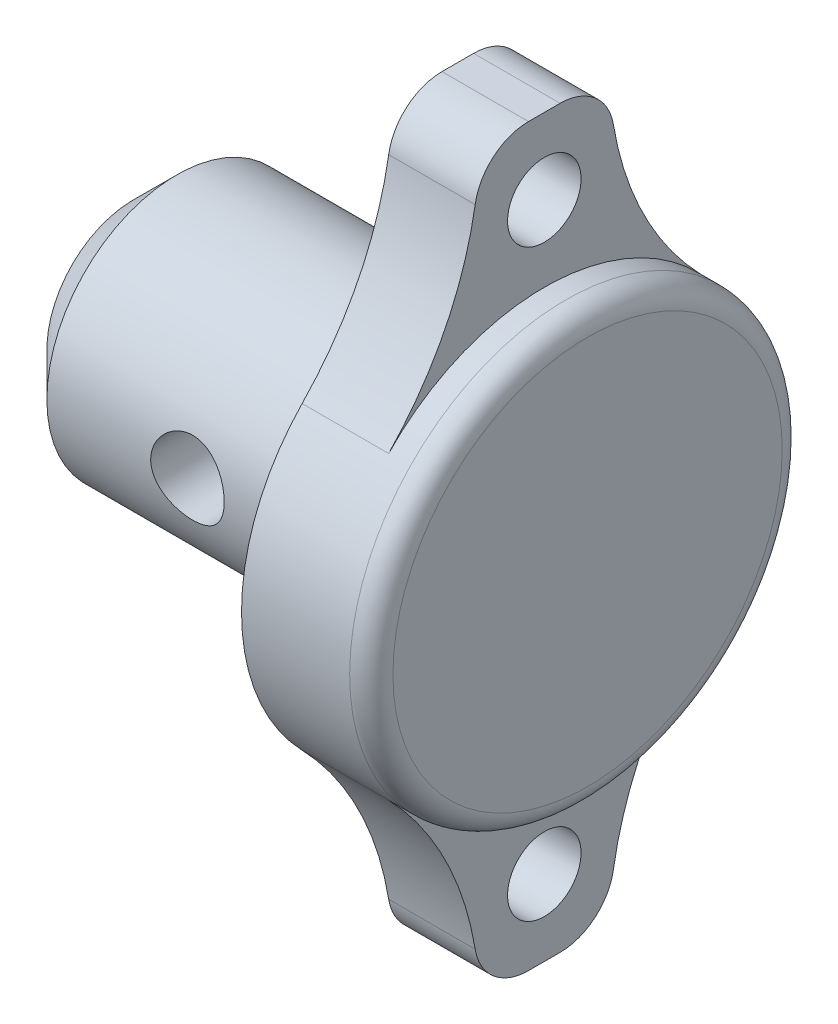
SolidWorks part; units mm, degrees
ref_plane "Alzado" through (0, 0, 0) normal (0, 0, 1) x (1, 0, 0)
ref_plane "Planta" through (0, 0, 0) normal (0, 1, 0) x (1, 0, 0)
ref_plane "Vista lateral" through (0, 0, 0) normal (1, 0, 0) x (0, 0, -1)
sketch "Croquis1" plane through (0, 0, 0) normal (1, 0, 0) x (0, 0, -1)
  circle A0 centre (0, 0) radius 6
  dimension "D1" = 12
extrude "Saliente-Extruir1" add sketch "Croquis1" along normal mid plane 15
sketch "Croquis2" plane through (7.5, 0, 0) normal (1, 0, 0) x (0, 0, -1)
  circle A0 centre (0, 0) radius 10
  dimension "D1" = 20
extrude "Saliente-Extruir2" add sketch "Croquis2" along normal blind 6
sketch "Croquis3" plane through (7.5, 0, 0) normal (-1, 0, 0) x (0, 0, 1)
  circle A0 centre (0, 0) radius 6
  circle A1 centre (0, 0) radius 8.5
  dimension "D1" = 17
extrude "Cortar-Extruir1" cut sketch "Croquis3" against normal blind 2.5
sketch "Croquis4" plane through (7.5, 0, 0) normal (-1, 0, 0) x (0, 0, 1)
  line L0 (0, 0) -> (0, -4.1911) construction
  line L1 (3, -9.5394) -> (3, -17)
  line L2 (3, -17) -> (-3, -17)
  line L3 (-3, -9.5394) -> (-3, -17)
  circle A2 centre (0, -13.5) radius 1.7
  circle A5 centre (0, 0) radius 10 construction
  arc A6 (-3, -9.5394) -> (3, -9.5394) centre (0, 0) ccw
  point P9 (0, -17)
  dimension "D3" = 3.4
  dimension "D1" = 6
  dimension "D2" = 17
  dimension "D4" = 13.5
extrude "Saliente-Extruir3" add sketch "Croquis4" against normal blind 4
fillet "Redondeo1" radius 15 2 edges at (9.5, -9.5394, -3) (9.5, -9.5394, 3)
sketch "Croquis5" plane through (0, 0, 0) normal (0, 0, 1) x (1, 0, 0)
  line L0 (7.5, 10) -> (7.5, -6.9415) construction
  circle A0 centre (1, 0) radius 1.7
  dimension "D1" = 3.4
  dimension "D2" = 6.5
extrude "Cortar-Extruir2" cut sketch "Croquis5" against normal mid plane 13
mirror "Simetría1" about plane through (0, 0, 0) normal (0, 1, 0) of "Redondeo1", "Saliente-Extruir3"
fillet "Redondeo2" radius 2.5 4 edges at (9.5, 17, -3) (9.5, 17, 3) (9.5, -17, -3) (9.5, -17, 3)
chamfer "Chaflán1" distance 2 angle 45 1 edges at (-7.5, 0, -6)
fillet "Redondeo3" radius 1 1 edges at (13.5, 0, -10)
